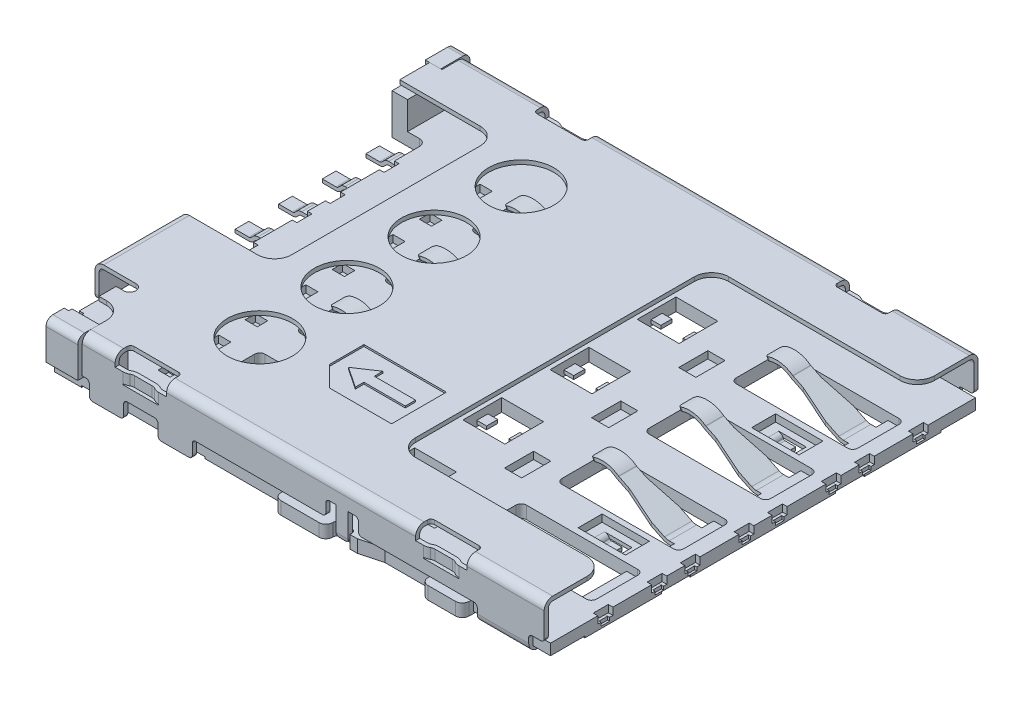
SolidWorks part; units mm, degrees
ref_plane "Front Plane" through (0, 0, 0) normal (0, 0, 1) x (1, 0, 0)
ref_plane "Top Plane" through (0, 0, 0) normal (0, 1, 0) x (1, 0, 0)
ref_plane "Right Plane" through (0, 0, 0) normal (1, 0, 0) x (0, 0, -1)
sketch "Sketch1" plane through (0, 0, 0) normal (0, 1, 0) x (1, 0, 0)
  line L0 (-7.5, 6.21) -> (-7.5, 4.64)
  line L1 (-7.5, 4.64) -> (-7.15, 4.64)
  line L2 (-6.95, 4.44) -> (-6.95, 3.71)
  line L6 (-6.95, 3.27) -> (-6.95, 2.14)
  line L10 (-6.95, 1.7) -> (-6.95, 1.17)
  line L14 (-6.95, 0.73) -> (-6.95, -0.4)
  line L18 (-6.95, -0.84) -> (-6.95, -1.37)
  line L22 (-6.95, -1.81) -> (-6.95, -2.94)
  line L26 (-6.95, -3.38) -> (-6.95, -3.91)
  line L29 (-6.815, -4.35) -> (-6.6639, -4.35) construction
  line L30 (-6.6639, -4.35) -> (-5.3139, -5.7) construction
  line L31 (-5.3139, -5.7) -> (-5.3139, -6.2) construction
  line L32 (-5.3139, -6.2) -> (-0.23, -6.2)
  line L33 (-0.23, -6.2) -> (-0.23, -6.32)
  line L34 (-0.03, -6.52) -> (1.08, -6.52)
  line L35 (1.28, -6.32) -> (1.28, -6.3)
  line L36 (1.38, -6.2) -> (1.73, -6.2)
  line L37 (1.83, -6.3) -> (1.83, -6.37)
  line L38 (1.83, -6.37) -> (2.0456, -6.37)
  line L39 (2.0456, -6.37) -> (2.68, -6.2)
  line L40 (2.68, -6.2) -> (4.06, -6.2)
  line L41 (4.06, -6.2) -> (4.06, -6.32)
  line L42 (4.26, -6.52) -> (5.06, -6.52)
  line L43 (5.26, -6.32) -> (5.26, -6.19)
  line L44 (5.26, -6.19) -> (7.5, -6.19)
  line L45 (7.5, -6.19) -> (7.5, -4.81)
  line L49 (7.5, -4.37) -> (7.5, -3.24)
  line L53 (7.5, -2.8) -> (7.5, -2.27)
  line L57 (7.5, -1.83) -> (7.5, -0.7)
  line L61 (7.5, -0.26) -> (7.5, 0.27)
  line L65 (7.5, 0.71) -> (7.5, 1.84)
  line L69 (7.5, 2.28) -> (7.5, 2.81)
  line L73 (7.5, 3.25) -> (7.5, 4.38)
  line L77 (7.5, 4.82) -> (7.5, 6.2)
  line L78 (7.5, 6.2) -> (5.26, 6.2)
  line L79 (5.26, 6.2) -> (5.26, 6.33)
  line L80 (5.06, 6.53) -> (4.26, 6.53)
  line L81 (4.06, 6.33) -> (4.06, 6.21)
  line L82 (4.06, 6.21) -> (2.68, 6.21)
  line L83 (2.68, 6.21) -> (2.0456, 6.38)
  line L84 (2.0456, 6.38) -> (1.83, 6.38)
  line L85 (1.83, 6.38) -> (1.83, 6.31)
  line L86 (1.73, 6.21) -> (1.38, 6.21)
  line L87 (1.28, 6.31) -> (1.28, 6.33)
  line L88 (1.08, 6.53) -> (-0.03, 6.53)
  line L89 (-0.23, 6.33) -> (-0.23, 6.21)
  line L90 (-0.23, 6.21) -> (-7.5, 6.21)
  line L91 (-7.5, 4.64) -> (-7.5, -6.2) construction
  line L92 (-7.5, -6.2) -> (-6.95, -6.2) construction
  line L93 (7.5, 6.2) -> (-7.5, -6.2) construction
  line L94 (-6.95, 3.71) -> (-6.95, 3.27)
  line L95 (-6.95, 2.14) -> (-6.95, 1.7)
  line L96 (-6.95, 1.17) -> (-6.95, 0.73)
  line L97 (-6.95, -0.4) -> (-6.95, -0.84)
  line L98 (-6.95, -1.37) -> (-6.95, -1.81)
  line L99 (-6.95, -2.94) -> (-6.95, -3.38)
  line L100 (-6.95, -3.91) -> (-6.95, -4.35)
  line L101 (-6.95, -4.35) -> (-6.815, -4.35) construction
  line L102 (7.5, -4.81) -> (7.5, -4.37)
  line L103 (7.5, -3.24) -> (7.5, -2.8)
  line L104 (7.5, -2.27) -> (7.5, -1.83)
  line L105 (7.5, -0.7) -> (7.5, -0.26)
  line L106 (7.5, 0.27) -> (7.5, 0.71)
  line L107 (7.5, 1.84) -> (7.5, 2.28)
  line L108 (7.5, 2.81) -> (7.5, 3.25)
  line L109 (7.5, 4.38) -> (7.5, 4.82)
  line L110 (-6.95, -4.35) -> (-6.95, -6.2)
  line L111 (-6.95, -6.2) -> (-5.3139, -6.2)
  arc A0 (-6.95, 4.44) -> (-7.15, 4.64) centre (-7.15, 4.44) ccw
  arc A1 (-0.23, -6.32) -> (-0.03, -6.52) centre (-0.03, -6.32) ccw
  arc A2 (1.08, -6.52) -> (1.28, -6.32) centre (1.08, -6.32) ccw
  arc A3 (1.38, -6.2) -> (1.28, -6.3) centre (1.38, -6.3) ccw
  arc A4 (1.83, -6.3) -> (1.73, -6.2) centre (1.73, -6.3) ccw
  arc A5 (4.06, -6.32) -> (4.26, -6.52) centre (4.26, -6.32) ccw
  arc A6 (5.06, -6.52) -> (5.26, -6.32) centre (5.06, -6.32) ccw
  arc A7 (5.26, 6.33) -> (5.06, 6.53) centre (5.06, 6.33) ccw
  arc A8 (4.26, 6.53) -> (4.06, 6.33) centre (4.26, 6.33) ccw
  arc A9 (1.73, 6.21) -> (1.83, 6.31) centre (1.73, 6.31) ccw
  arc A10 (1.28, 6.31) -> (1.38, 6.21) centre (1.38, 6.31) ccw
  arc A11 (1.28, 6.33) -> (1.08, 6.53) centre (1.08, 6.33) ccw
  arc A12 (-0.03, 6.53) -> (-0.23, 6.33) centre (-0.03, 6.33) ccw
extrude "Boss-Extrude1" add sketch "Sketch1" along normal blind 0.37
sketch "Sketch2" plane through (-58.2789, 0.37, -33.3165) normal (0, 1, 0) x (1, 0, 0)
  line L0 (60.6874, -30.6765) -> (61.1874, -30.6765)
  line L1 (61.1874, -30.6765) -> (61.1874, -29.8265)
  line L2 (61.1874, -29.8265) -> (60.6874, -29.8265)
  line L3 (60.6874, -29.8265) -> (60.6874, -30.6765)
  line L4 (61.1874, -33.2165) -> (61.1874, -32.3665)
  line L5 (60.6874, -33.2165) -> (61.1874, -33.2165)
  line L6 (60.6874, -32.3665) -> (60.6874, -33.2165)
  line L7 (60.6874, -32.3665) -> (61.1874, -32.3665)
  line L8 (61.1874, -35.7565) -> (61.1874, -34.9065)
  line L9 (61.1874, -34.9065) -> (60.6874, -34.9065)
  line L10 (60.6874, -34.9065) -> (60.6874, -35.7565)
  line L11 (60.6874, -35.7565) -> (61.1874, -35.7565)
  line L12 (60.6874, -38.2965) -> (61.1874, -38.2965)
  line L13 (61.1874, -37.4465) -> (61.1874, -38.2965)
  line L14 (61.1874, -37.4465) -> (60.6874, -37.4465)
  line L15 (60.6874, -37.4465) -> (60.6874, -38.2965)
  line L16 (60.0874, -36.5565) -> (60.0874, -37.6865)
  line L17 (60.0874, -37.6865) -> (58.8674, -37.6865)
  line L18 (58.8674, -36.5565) -> (58.8674, -37.6865)
  line L19 (60.0874, -36.5565) -> (58.8674, -36.5565)
  line L20 (60.0874, -34.0165) -> (60.0874, -35.1465)
  line L21 (60.0874, -35.1465) -> (58.8674, -35.1465)
  line L22 (58.8674, -34.0165) -> (58.8674, -35.1465)
  line L23 (60.0874, -34.0165) -> (58.8674, -34.0165)
  line L24 (60.0874, -31.4765) -> (60.0874, -32.6065)
  line L25 (60.0874, -32.6065) -> (58.8674, -32.6065)
  line L26 (58.8674, -31.4765) -> (58.8674, -32.6065)
  line L27 (60.0874, -31.4765) -> (58.8674, -31.4765)
  line L28 (60.0874, -30.0665) -> (58.8674, -30.0665)
  line L29 (60.0874, -28.9365) -> (60.0874, -30.0665)
  line L30 (60.0874, -28.9365) -> (58.8674, -28.9365)
  line L31 (58.8674, -28.9365) -> (58.8674, -30.0665)
  line L32 (53.5174, -38.029) -> (53.5174, -38.334)
  line L33 (53.1624, -38.334) -> (53.5174, -38.334)
  line L34 (53.1624, -38.029) -> (53.1624, -38.334)
  line L35 (53.1624, -38.029) -> (53.5174, -38.029)
  line L36 (53.1624, -37.294) -> (53.5174, -37.294)
  line L37 (53.5174, -37.294) -> (53.5174, -36.564)
  line L38 (53.1624, -36.564) -> (53.5174, -36.564)
  line L39 (53.1624, -36.564) -> (53.1624, -37.294)
  line L40 (53.5174, -35.794) -> (53.5174, -35.489)
  line L41 (53.1624, -35.794) -> (53.5174, -35.794)
  line L42 (53.1624, -35.489) -> (53.1624, -35.794)
  line L43 (53.1624, -35.489) -> (53.5174, -35.489)
  line L44 (53.5174, -34.754) -> (53.5174, -34.024)
  line L45 (53.1624, -34.754) -> (53.5174, -34.754)
  line L46 (53.1624, -34.024) -> (53.1624, -34.754)
  line L47 (53.5174, -34.024) -> (53.1624, -34.024)
  line L48 (53.1624, -32.949) -> (53.1624, -33.254)
  line L49 (53.1624, -33.254) -> (53.5174, -33.254)
  line L50 (53.5174, -33.254) -> (53.5174, -32.949)
  line L51 (53.1624, -32.949) -> (53.5174, -32.949)
  line L52 (53.1624, -32.214) -> (53.5174, -32.214)
  line L53 (53.5174, -32.214) -> (53.5174, -31.484)
  line L54 (53.1624, -31.484) -> (53.1624, -32.214)
  line L55 (53.1624, -31.484) -> (53.5174, -31.484)
  line L56 (53.1624, -30.714) -> (53.5174, -30.714)
  line L57 (53.5174, -30.714) -> (53.5174, -30.409)
  line L58 (53.5174, -30.409) -> (53.1624, -30.409)
  line L59 (53.1624, -30.409) -> (53.1624, -30.714)
  line L60 (53.1624, -29.674) -> (53.5174, -29.674)
  line L61 (53.5174, -29.674) -> (53.5174, -28.944)
  line L62 (53.5174, -28.944) -> (53.1624, -28.944)
  line L63 (53.1624, -28.944) -> (53.1624, -29.674)
  line L64 (61.7874, -37.7215) -> (61.7874, -36.5215)
  line L65 (65.1874, -37.8715) -> (61.9374, -37.8715)
  line L66 (65.3374, -36.5215) -> (65.3374, -37.7215)
  line L67 (61.9374, -36.3715) -> (65.1874, -36.3715)
  line L68 (65.1874, -35.3315) -> (61.9374, -35.3315)
  line L69 (65.3374, -33.9815) -> (65.3374, -35.1815)
  line L70 (61.9374, -33.8315) -> (65.1874, -33.8315)
  line L71 (61.7874, -35.1815) -> (61.7874, -33.9815)
  line L72 (61.7874, -32.6415) -> (61.7874, -31.4415)
  line L73 (65.1874, -32.7915) -> (61.9374, -32.7915)
  line L74 (65.3374, -31.4415) -> (65.3374, -32.6415)
  line L75 (61.9374, -31.2915) -> (65.1874, -31.2915)
  line L76 (65.1874, -30.2515) -> (61.9374, -30.2515)
  line L77 (65.3374, -28.9015) -> (65.3374, -30.1015)
  line L78 (61.9374, -28.7515) -> (65.1874, -28.7515)
  line L79 (61.7874, -30.1015) -> (61.7874, -28.9015)
  line L80 (54.3174, -31.2915) -> (57.5674, -31.2915)
  line L81 (54.1674, -32.6415) -> (54.1674, -31.4415)
  line L82 (57.5674, -32.7915) -> (54.3174, -32.7915)
  line L83 (54.3174, -33.8315) -> (57.5674, -33.8315)
  line L84 (54.1674, -35.1815) -> (54.1674, -33.9815)
  line L85 (57.5674, -35.3315) -> (54.3174, -35.3315)
  line L86 (54.1674, -37.7215) -> (54.1674, -36.5215)
  line L87 (57.5674, -37.8715) -> (54.3174, -37.8715)
  line L88 (54.3174, -36.3715) -> (57.5674, -36.3715)
  line L89 (57.7174, -36.5215) -> (57.7174, -37.7215)
  line L90 (57.7174, -33.9815) -> (57.7174, -35.1815)
  line L91 (57.7174, -31.4415) -> (57.7174, -32.6415)
  line L92 (57.7174, -28.9015) -> (57.7174, -30.1015)
  line L93 (54.3174, -28.7515) -> (57.5674, -28.7515)
  line L94 (54.1674, -30.1015) -> (54.1674, -28.9015)
  line L95 (57.5674, -30.2515) -> (54.3174, -30.2515)
  line L96 (64.6489, -30.4315) -> (64.6489, -31.1315)
  line L97 (63.2689, -30.4315) -> (64.6489, -30.4315)
  line L98 (63.2689, -31.1315) -> (63.2689, -30.4315)
  line L99 (64.6489, -31.1315) -> (63.2689, -31.1315)
  line L100 (63.2689, -36.1915) -> (64.6489, -36.1915)
  line L101 (64.6489, -35.4915) -> (64.6489, -36.1915)
  line L102 (64.6489, -35.4915) -> (63.2689, -35.4915)
  line L103 (63.2689, -36.1915) -> (63.2689, -35.4915)
  arc A0 (61.7874, -37.7215) -> (61.9374, -37.8715) centre (61.9374, -37.7215) ccw
  arc A1 (65.1874, -37.8715) -> (65.3374, -37.7215) centre (65.1874, -37.7215) ccw
  arc A2 (65.3374, -36.5215) -> (65.1874, -36.3715) centre (65.1874, -36.5215) ccw
  arc A3 (61.9374, -36.3715) -> (61.7874, -36.5215) centre (61.9374, -36.5215) ccw
  arc A4 (61.7874, -35.1815) -> (61.9374, -35.3315) centre (61.9374, -35.1815) ccw
  arc A5 (65.1874, -35.3315) -> (65.3374, -35.1815) centre (65.1874, -35.1815) ccw
  arc A6 (65.3374, -33.9815) -> (65.1874, -33.8315) centre (65.1874, -33.9815) ccw
  arc A7 (61.9374, -33.8315) -> (61.7874, -33.9815) centre (61.9374, -33.9815) ccw
  arc A8 (61.7874, -32.6415) -> (61.9374, -32.7915) centre (61.9374, -32.6415) ccw
  arc A9 (65.1874, -32.7915) -> (65.3374, -32.6415) centre (65.1874, -32.6415) ccw
  arc A10 (65.3374, -31.4415) -> (65.1874, -31.2915) centre (65.1874, -31.4415) ccw
  arc A11 (61.9374, -31.2915) -> (61.7874, -31.4415) centre (61.9374, -31.4415) ccw
  arc A12 (61.7874, -30.1015) -> (61.9374, -30.2515) centre (61.9374, -30.1015) ccw
  arc A13 (65.1874, -30.2515) -> (65.3374, -30.1015) centre (65.1874, -30.1015) ccw
  arc A14 (65.3374, -28.9015) -> (65.1874, -28.7515) centre (65.1874, -28.9015) ccw
  arc A15 (61.9374, -28.7515) -> (61.7874, -28.9015) centre (61.9374, -28.9015) ccw
  arc A16 (54.3174, -31.2915) -> (54.1674, -31.4415) centre (54.3174, -31.4415) ccw
  arc A17 (54.1674, -32.6415) -> (54.3174, -32.7915) centre (54.3174, -32.6415) ccw
  arc A18 (57.7174, -31.4415) -> (57.5674, -31.2915) centre (57.5674, -31.4415) ccw
  arc A19 (57.5674, -32.7915) -> (57.7174, -32.6415) centre (57.5674, -32.6415) ccw
  arc A20 (57.7174, -33.9815) -> (57.5674, -33.8315) centre (57.5674, -33.9815) ccw
  arc A21 (54.3174, -33.8315) -> (54.1674, -33.9815) centre (54.3174, -33.9815) ccw
  arc A22 (54.1674, -35.1815) -> (54.3174, -35.3315) centre (54.3174, -35.1815) ccw
  arc A23 (57.5674, -35.3315) -> (57.7174, -35.1815) centre (57.5674, -35.1815) ccw
  arc A24 (54.3174, -36.3715) -> (54.1674, -36.5215) centre (54.3174, -36.5215) ccw
  arc A25 (54.1674, -37.7215) -> (54.3174, -37.8715) centre (54.3174, -37.7215) ccw
  arc A26 (57.5674, -37.8715) -> (57.7174, -37.7215) centre (57.5674, -37.7215) ccw
  arc A27 (57.7174, -36.5215) -> (57.5674, -36.3715) centre (57.5674, -36.5215) ccw
  arc A28 (57.5674, -30.2515) -> (57.7174, -30.1015) centre (57.5674, -30.1015) ccw
  arc A29 (57.7174, -28.9015) -> (57.5674, -28.7515) centre (57.5674, -28.9015) ccw
  arc A30 (54.3174, -28.7515) -> (54.1674, -28.9015) centre (54.3174, -28.9015) ccw
  arc A31 (54.1674, -30.1015) -> (54.3174, -30.2515) centre (54.3174, -30.1015) ccw
extrude "Cut-Extrude1" cut sketch "Sketch2" against normal through all
sketch "Sketch3" plane through (0, 0.37, 0) normal (0, 1, 0) x (1, 0, 0)
  line L0 (7.5, -4.81) -> (7.365, -4.81)
  line L1 (7.365, -4.37) -> (7.365, -4.81)
  line L2 (7.365, -4.37) -> (7.5, -4.37)
  line L3 (7.5, -3.24) -> (7.365, -3.24)
  line L4 (7.365, -3.24) -> (7.365, -2.8)
  line L5 (7.5, -2.8) -> (7.365, -2.8)
  line L6 (7.5, -2.27) -> (7.365, -2.27)
  line L7 (7.365, -1.83) -> (7.365, -2.27)
  line L8 (7.5, -1.83) -> (7.365, -1.83)
  line L9 (7.5, -0.7) -> (7.365, -0.7)
  line L10 (7.365, -0.7) -> (7.365, -0.26)
  line L11 (7.365, -0.26) -> (7.5, -0.26)
  line L12 (7.365, 0.27) -> (7.5, 0.27)
  line L13 (7.365, 0.71) -> (7.365, 0.27)
  line L14 (7.365, 0.71) -> (7.5, 0.71)
  line L15 (7.5, 1.84) -> (7.365, 1.84)
  line L16 (7.365, 1.84) -> (7.365, 2.28)
  line L17 (7.5, 2.28) -> (7.365, 2.28)
  line L18 (7.5, 2.81) -> (7.365, 2.81)
  line L19 (7.365, 3.25) -> (7.365, 2.81)
  line L20 (7.365, 3.25) -> (7.5, 3.25)
  line L21 (7.365, 4.38) -> (7.5, 4.38)
  line L22 (7.365, 4.38) -> (7.365, 4.82)
  line L23 (7.5, 4.82) -> (7.365, 4.82)
  line L24 (-6.95, -5.92) -> (-6.815, -5.92)
  line L25 (-6.815, -5.92) -> (-6.815, -5.48)
  line L27 (-6.95, -5.48) -> (-6.815, -5.48)
  line L28 (-6.95, -4.35) -> (-6.815, -4.35)
  line L29 (-6.815, -4.35) -> (-6.815, -3.91)
  line L30 (-6.95, -3.91) -> (-6.815, -3.91)
  line L31 (-6.815, -3.38) -> (-6.95, -3.38)
  line L32 (-6.815, -2.94) -> (-6.815, -3.38)
  line L33 (-6.815, -2.94) -> (-6.95, -2.94)
  line L34 (-6.815, -1.81) -> (-6.95, -1.81)
  line L35 (-6.815, -1.81) -> (-6.815, -1.37)
  line L36 (-6.815, -1.37) -> (-6.95, -1.37)
  line L37 (-6.815, -0.84) -> (-6.95, -0.84)
  line L38 (-6.815, -0.4) -> (-6.815, -0.84)
  line L39 (-6.815, -0.4) -> (-6.95, -0.4)
  line L40 (-6.815, 0.73) -> (-6.95, 0.73)
  line L41 (-6.815, 0.73) -> (-6.815, 1.17)
  line L42 (-6.95, 1.17) -> (-6.815, 1.17)
  line L43 (-6.815, 1.7) -> (-6.95, 1.7)
  line L44 (-6.815, 2.14) -> (-6.815, 1.7)
  line L45 (-6.95, 2.14) -> (-6.815, 2.14)
  line L46 (-6.95, 3.27) -> (-6.815, 3.27)
  line L47 (-6.815, 3.27) -> (-6.815, 3.71)
  line L48 (-6.815, 3.71) -> (-6.95, 3.71)
  line L49 (-6.95, -4.35) -> (-6.95, -3.91)
  line L50 (-6.95, -3.38) -> (-6.95, -2.94)
  line L51 (-6.95, -1.81) -> (-6.95, -1.37)
  line L52 (-6.95, -0.84) -> (-6.95, -0.4)
  line L53 (-6.95, 0.73) -> (-6.95, 1.17)
  line L54 (-6.95, 1.7) -> (-6.95, 2.14)
  line L55 (-6.95, 3.27) -> (-6.95, 3.71)
  line L56 (7.5, 4.38) -> (7.5, 4.82)
  line L57 (7.5, 2.81) -> (7.5, 3.25)
  line L58 (7.5, 1.84) -> (7.5, 2.28)
  line L59 (7.5, 0.27) -> (7.5, 0.71)
  line L60 (7.5, -0.7) -> (7.5, -0.26)
  line L61 (7.5, -2.27) -> (7.5, -1.83)
  line L62 (7.5, -3.24) -> (7.5, -2.8)
  line L63 (7.5, -4.81) -> (7.5, -4.37)
  line L64 (-6.95, -5.92) -> (-6.95, -5.48)
extrude "Cut-Extrude2" cut sketch "Sketch3" against normal blind 0.21
sketch "Sketch4" plane through (0, 0.16, 0) normal (0, 1, 0) x (1, 0, 0)
  line L0 (7.5, -4.465) -> (7.365, -4.465)
  line L1 (7.365, -4.715) -> (7.5, -4.715)
  line L2 (7.5, -2.895) -> (7.365, -2.895)
  line L3 (7.365, -3.145) -> (7.5, -3.145)
  line L4 (7.5, -1.925) -> (7.365, -1.925)
  line L5 (7.365, -2.175) -> (7.5, -2.175)
  line L6 (7.5, -0.355) -> (7.365, -0.355)
  line L7 (7.365, -0.605) -> (7.5, -0.605)
  line L8 (7.5, 0.615) -> (7.365, 0.615)
  line L9 (7.365, 0.365) -> (7.5, 0.365)
  line L10 (7.5, 2.185) -> (7.365, 2.185)
  line L11 (7.365, 1.935) -> (7.5, 1.935)
  line L12 (7.5, 3.155) -> (7.365, 3.155)
  line L13 (7.365, 2.905) -> (7.5, 2.905)
  line L14 (7.5, 4.725) -> (7.365, 4.725)
  line L15 (7.365, 4.475) -> (7.5, 4.475)
  line L16 (-6.95, -5.575) -> (-6.815, -5.575)
  line L17 (-6.95, -5.825) -> (-6.815, -5.825)
  line L18 (-6.95, -4.255) -> (-6.815, -4.255)
  line L19 (-6.815, -4.005) -> (-6.95, -4.005)
  line L20 (-6.95, -3.285) -> (-6.815, -3.285)
  line L21 (-6.815, -3.035) -> (-6.95, -3.035)
  line L22 (-6.95, -1.715) -> (-6.815, -1.715)
  line L23 (-6.815, -1.465) -> (-6.95, -1.465)
  line L24 (-6.95, -0.745) -> (-6.815, -0.745)
  line L25 (-6.815, -0.495) -> (-6.95, -0.495)
  line L26 (-6.95, 0.825) -> (-6.815, 0.825)
  line L27 (-6.815, 1.075) -> (-6.95, 1.075)
  line L28 (-6.95, 1.795) -> (-6.815, 1.795)
  line L29 (-6.815, 2.045) -> (-6.95, 2.045)
  line L30 (-6.95, 3.365) -> (-6.815, 3.365)
  line L31 (-6.815, 3.615) -> (-6.95, 3.615)
  line L32 (-6.95, 3.615) -> (-6.95, 3.365)
  line L33 (-6.95, 2.045) -> (-6.95, 1.795)
  line L34 (-6.95, 1.075) -> (-6.95, 0.825)
  line L35 (-6.95, -0.495) -> (-6.95, -0.745)
  line L36 (-6.95, -1.465) -> (-6.95, -1.715)
  line L37 (-6.95, -3.035) -> (-6.95, -3.285)
  line L38 (-6.95, -4.005) -> (-6.95, -4.255)
  line L39 (7.5, 4.725) -> (7.5, 4.475)
  line L40 (7.5, 3.155) -> (7.5, 2.905)
  line L41 (7.5, 2.185) -> (7.5, 1.935)
  line L42 (7.5, 0.615) -> (7.5, 0.365)
  line L43 (7.5, -0.355) -> (7.5, -0.605)
  line L44 (7.5, -1.925) -> (7.5, -2.175)
  line L45 (7.5, -2.895) -> (7.5, -3.145)
  line L46 (7.5, -4.465) -> (7.5, -4.715)
  line L47 (-6.815, 3.615) -> (-6.815, 3.365)
  line L48 (-6.815, 2.045) -> (-6.815, 1.795)
  line L50 (-6.815, 1.075) -> (-6.815, 0.825)
  line L52 (-6.815, -0.745) -> (-6.815, -0.495)
  line L54 (-6.815, -1.715) -> (-6.815, -1.465)
  line L56 (-6.815, -3.285) -> (-6.815, -3.035)
  line L59 (-6.815, -4.005) -> (-6.815, -4.255)
  line L61 (7.365, 4.725) -> (7.365, 4.475)
  line L62 (7.365, 3.155) -> (7.365, 2.905)
  line L64 (7.365, 2.185) -> (7.365, 1.935)
  line L65 (7.365, 0.615) -> (7.365, 0.365)
  line L67 (7.365, -0.605) -> (7.365, -0.355)
  line L69 (7.365, -1.925) -> (7.365, -2.175)
  line L72 (7.365, -2.895) -> (7.365, -3.145)
  line L74 (7.365, -4.465) -> (7.365, -4.715)
  line L76 (-6.815, -5.575) -> (-6.815, -5.825)
  line L78 (-6.95, -5.825) -> (-6.95, -5.575)
extrude "Cut-Extrude3" cut sketch "Sketch4" against normal blind 0.1
sketch "Sketch5" plane through (0, 0.06, 0) normal (0, 1, 0) x (1, 0, 0)
  line L0 (-6.65, 3.615) -> (-6.89, 3.615)
  line L1 (-6.89, 3.615) -> (-6.89, 3.365)
  line L2 (-6.89, 3.365) -> (-6.8, 3.365)
  line L3 (-6.8, 3.365) -> (-6.8, 2.045)
  line L4 (-6.8, 2.045) -> (-6.89, 2.045)
  line L5 (-6.89, 2.045) -> (-6.89, 1.795)
  line L6 (-6.89, 1.795) -> (-6.8, 1.795)
  line L7 (-6.8, 1.795) -> (-6.8, 1.075)
  line L8 (-6.8, 1.075) -> (-6.89, 1.075)
  line L9 (-6.89, 1.075) -> (-6.89, 0.825)
  line L10 (-6.89, 0.825) -> (-6.8, 0.825)
  line L11 (-6.8, 0.825) -> (-6.8, -0.495)
  line L12 (-6.8, -0.495) -> (-6.89, -0.495)
  line L13 (-6.89, -0.495) -> (-6.89, -0.745)
  line L14 (-6.89, -0.745) -> (-6.8, -0.745)
  line L15 (-6.8, -0.745) -> (-6.8, -1.465)
  line L16 (-6.8, -1.465) -> (-6.89, -1.465)
  line L17 (-6.89, -1.465) -> (-6.89, -1.715)
  line L18 (-6.89, -1.715) -> (-6.8, -1.715)
  line L19 (-6.8, -1.715) -> (-6.8, -3.035)
  line L20 (-6.8, -3.035) -> (-6.89, -3.035)
  line L21 (-6.89, -3.035) -> (-6.89, -3.285)
  line L22 (-6.89, -3.285) -> (-6.8, -3.285)
  line L23 (-6.8, -3.285) -> (-6.8, -4.005)
  line L24 (-6.8, -4.005) -> (-6.89, -4.005)
  line L25 (-6.89, -4.005) -> (-6.89, -4.255)
  line L26 (-6.89, -4.255) -> (-6.8, -4.255)
  line L27 (-6.8, -4.255) -> (-6.8, -5.575)
  line L28 (-6.8, -5.575) -> (-6.89, -5.575)
  line L29 (-6.89, -5.575) -> (-6.89, -5.825)
  line L30 (-6.89, -5.825) -> (-6.65, -5.825)
  line L31 (-6.65, -5.825) -> (-6.65, 3.615)
  line L32 (7.2, -4.715) -> (7.44, -4.715)
  line L33 (7.44, -4.715) -> (7.44, -4.465)
  line L34 (7.44, -4.465) -> (7.35, -4.465)
  line L35 (7.35, -4.465) -> (7.35, -3.145)
  line L36 (7.35, -3.145) -> (7.44, -3.145)
  line L37 (7.44, -3.145) -> (7.44, -2.895)
  line L38 (7.44, -2.895) -> (7.35, -2.895)
  line L39 (7.35, -2.895) -> (7.35, -2.175)
  line L40 (7.35, -2.175) -> (7.44, -2.175)
  line L41 (7.44, -2.175) -> (7.44, -1.925)
  line L42 (7.44, -1.925) -> (7.35, -1.925)
  line L43 (7.35, -1.925) -> (7.35, -0.605)
  line L44 (7.35, -0.605) -> (7.44, -0.605)
  line L45 (7.44, -0.605) -> (7.44, -0.355)
  line L46 (7.44, -0.355) -> (7.35, -0.355)
  line L47 (7.35, -0.355) -> (7.35, 0.365)
  line L48 (7.35, 0.365) -> (7.44, 0.365)
  line L49 (7.44, 0.365) -> (7.44, 0.615)
  line L50 (7.44, 0.615) -> (7.35, 0.615)
  line L51 (7.35, 0.615) -> (7.35, 1.935)
  line L52 (7.35, 1.935) -> (7.44, 1.935)
  line L53 (7.44, 1.935) -> (7.44, 2.185)
  line L54 (7.44, 2.185) -> (7.35, 2.185)
  line L55 (7.35, 2.185) -> (7.35, 2.905)
  line L56 (7.35, 2.905) -> (7.44, 2.905)
  line L57 (7.44, 2.905) -> (7.44, 3.155)
  line L58 (7.44, 3.155) -> (7.35, 3.155)
  line L59 (7.35, 3.155) -> (7.35, 4.475)
  line L60 (7.35, 4.475) -> (7.44, 4.475)
  line L61 (7.44, 4.475) -> (7.44, 4.725)
  line L62 (7.44, 4.725) -> (7.2, 4.725)
  line L63 (7.2, 4.725) -> (7.2, -4.715)
  line L64 (6.5855, 4.215) -> (6.4355, 4.215)
  line L65 (6.4355, 4.215) -> (6.4355, 3.415)
  line L66 (6.4355, 3.415) -> (6.5855, 3.415)
  line L67 (6.5855, 3.415) -> (6.5855, 1.675)
  line L68 (6.5855, 1.675) -> (6.4355, 1.675)
  line L69 (6.4355, 1.675) -> (6.4355, 0.875)
  line L70 (6.4355, 0.875) -> (6.5855, 0.875)
  line L71 (6.5855, 0.875) -> (6.5855, -0.865)
  line L72 (6.5855, -0.865) -> (6.4355, -0.865)
  line L73 (6.4355, -0.865) -> (6.4355, -1.665)
  line L74 (6.4355, -1.665) -> (6.5855, -1.665)
  line L75 (6.5855, -1.665) -> (6.5855, -4.555)
  line L76 (6.5855, -4.555) -> (7.0585, -4.555)
  line L77 (7.0585, -4.555) -> (7.0585, 4.565)
  line L78 (7.0585, 4.565) -> (6.5855, 4.565)
  line L79 (6.5855, 4.565) -> (6.5855, 4.215)
  line L80 (-1.0345, 4.215) -> (-1.1845, 4.215)
  line L81 (-1.1845, 4.215) -> (-1.1845, 3.415)
  line L82 (-1.1845, 3.415) -> (-1.0345, 3.415)
  line L83 (-1.0345, 3.415) -> (-1.0345, 1.675)
  line L84 (-1.0345, 1.675) -> (-1.1845, 1.675)
  line L85 (-1.1845, 1.675) -> (-1.1845, 0.875)
  line L86 (-1.1845, 0.875) -> (-1.0345, 0.875)
  line L87 (-1.0345, 0.875) -> (-1.0345, -0.865)
  line L88 (-1.0345, -0.865) -> (-1.1845, -0.865)
  line L89 (-1.1845, -0.865) -> (-1.1845, -1.665)
  line L90 (-1.1845, -1.665) -> (-1.0345, -1.665)
  line L91 (-1.0345, -1.665) -> (-1.0345, -4.555)
  line L92 (-1.0345, -4.555) -> (-0.5615, -4.555)
  line L93 (-0.5615, -4.555) -> (-0.5615, 4.565)
  line L94 (-0.5615, 4.565) -> (-1.0345, 4.565)
  line L95 (-1.0345, 4.565) -> (-1.0345, 4.215)
  line L96 (2.4085, -4.13) -> (2.4085, -4.98)
  line L97 (2.4085, -4.98) -> (2.9085, -4.98)
  line L98 (2.9085, -4.98) -> (2.9085, -4.13)
  line L99 (2.9085, -4.13) -> (2.4085, -4.13)
  line L100 (2.4085, -1.59) -> (2.4085, -2.44)
  line L101 (2.4085, -2.44) -> (2.9085, -2.44)
  line L102 (2.9085, -2.44) -> (2.9085, -1.59)
  line L103 (2.9085, -1.59) -> (2.4085, -1.59)
  line L104 (1.5235, -3.6425) -> (1.5235, -3.9675)
  line L105 (1.5235, -3.9675) -> (1.8085, -3.9675)
  line L106 (1.8085, -3.9675) -> (1.8085, -3.6425)
  line L107 (1.8085, -3.6425) -> (1.5235, -3.6425)
  line L108 (0.5885, -3.6425) -> (0.5885, -3.9675)
  line L109 (0.5885, -3.9675) -> (0.8735, -3.9675)
  line L110 (0.8735, -3.9675) -> (0.8735, -3.6425)
  line L111 (0.8735, -3.6425) -> (0.5885, -3.6425)
  line L112 (0.5885, -1.1025) -> (0.5885, -1.4275)
  line L113 (0.5885, -1.4275) -> (0.8735, -1.4275)
  line L114 (0.8735, -1.4275) -> (0.8735, -1.1025)
  line L115 (0.8735, -1.1025) -> (0.5885, -1.1025)
  line L116 (1.5235, -1.1025) -> (1.5235, -1.4275)
  line L117 (1.5235, -1.4275) -> (1.8085, -1.4275)
  line L118 (1.8085, -1.4275) -> (1.8085, -1.1025)
  line L119 (1.8085, -1.1025) -> (1.5235, -1.1025)
  line L120 (2.4085, 0.95) -> (2.4085, 0.1)
  line L121 (2.4085, 0.1) -> (2.9085, 0.1)
  line L122 (2.9085, 0.1) -> (2.9085, 0.95)
  line L123 (2.9085, 0.95) -> (2.4085, 0.95)
  line L124 (0.5885, 1.4375) -> (0.5885, 1.1125)
  line L125 (0.5885, 1.1125) -> (0.8735, 1.1125)
  line L126 (0.8735, 1.1125) -> (0.8735, 1.4375)
  line L127 (0.8735, 1.4375) -> (0.5885, 1.4375)
  line L128 (1.5235, 1.4375) -> (1.5235, 1.1125)
  line L129 (1.5235, 1.1125) -> (1.8085, 1.1125)
  line L130 (1.8085, 1.1125) -> (1.8085, 1.4375)
  line L131 (1.8085, 1.4375) -> (1.5235, 1.4375)
  line L132 (2.4085, 3.49) -> (2.4085, 2.64)
  line L133 (2.4085, 2.64) -> (2.9085, 2.64)
  line L134 (2.9085, 2.64) -> (2.9085, 3.49)
  line L135 (2.9085, 3.49) -> (2.4085, 3.49)
  line L136 (1.5235, 3.9775) -> (1.5235, 3.6525)
  line L137 (1.5235, 3.6525) -> (1.8085, 3.6525)
  line L138 (1.8085, 3.6525) -> (1.8085, 3.9775)
  line L139 (1.8085, 3.9775) -> (1.5235, 3.9775)
  line L140 (0.5885, 3.9775) -> (0.5885, 3.6525)
  line L141 (0.5885, 3.6525) -> (0.8735, 3.6525)
  line L142 (0.8735, 3.6525) -> (0.8735, 3.9775)
  line L143 (0.8735, 3.9775) -> (0.5885, 3.9775)
  line L144 (-5.1165, 4.3725) -> (-5.1165, 3.6425)
  line L145 (-5.1165, 3.6425) -> (-4.7615, 3.6425)
  line L146 (-4.7615, 3.6425) -> (-4.7615, 4.3725)
  line L147 (-4.7615, 4.3725) -> (-5.1165, 4.3725)
  line L148 (-5.1165, 2.9075) -> (-5.1165, 2.6025)
  line L149 (-5.1165, 2.6025) -> (-4.7615, 2.6025)
  line L150 (-4.7615, 2.6025) -> (-4.7615, 2.9075)
  line L151 (-4.7615, 2.9075) -> (-5.1165, 2.9075)
  line L152 (-5.1165, 1.8325) -> (-5.1165, 1.1025)
  line L153 (-5.1165, 1.1025) -> (-4.7615, 1.1025)
  line L154 (-4.7615, 1.1025) -> (-4.7615, 1.8325)
  line L155 (-4.7615, 1.8325) -> (-5.1165, 1.8325)
  line L156 (-5.1165, 0.3675) -> (-5.1165, 0.0625)
  line L157 (-5.1165, 0.0625) -> (-4.7615, 0.0625)
  line L158 (-4.7615, 0.0625) -> (-4.7615, 0.3675)
  line L159 (-4.7615, 0.3675) -> (-5.1165, 0.3675)
  line L160 (-5.1165, -4.7125) -> (-5.1165, -5.0175)
  line L161 (-5.1165, -5.0175) -> (-4.7615, -5.0175)
  line L162 (-4.7615, -5.0175) -> (-4.7615, -4.7125)
  line L163 (-4.7615, -4.7125) -> (-5.1165, -4.7125)
  line L164 (-5.1165, -3.2475) -> (-5.1165, -3.9775)
  line L165 (-5.1165, -3.9775) -> (-4.7615, -3.9775)
  line L166 (-4.7615, -3.9775) -> (-4.7615, -3.2475)
  line L167 (-4.7615, -3.2475) -> (-5.1165, -3.2475)
  line L168 (-5.1165, -2.1725) -> (-5.1165, -2.4775)
  line L169 (-5.1165, -2.4775) -> (-4.7615, -2.4775)
  line L170 (-4.7615, -2.4775) -> (-4.7615, -2.1725)
  line L171 (-4.7615, -2.1725) -> (-5.1165, -2.1725)
  line L172 (-5.1165, -0.7075) -> (-5.1165, -1.4375)
  line L173 (-5.1165, -1.4375) -> (-4.7615, -1.4375)
  line L174 (-4.7615, -1.4375) -> (-4.7615, -0.7075)
  line L175 (-4.7615, -0.7075) -> (-5.1165, -0.7075)
  line L176 (-6.95, -2.125) -> (-7.2357, -2.125)
  line L177 (-7.2357, -2.125) -> (-7.2357, -2.525)
  line L178 (-7.2357, -2.525) -> (-6.95, -2.525)
  line L179 (-6.95, -2.525) -> (-6.95, -2.125)
  line L180 (-6.95, -0.855) -> (-7.2357, -0.855)
  line L181 (-7.2357, -0.855) -> (-7.2357, -1.255)
  line L182 (-7.2357, -1.255) -> (-6.95, -1.255)
  line L183 (-6.95, -1.255) -> (-6.95, -0.855)
  line L184 (-6.95, 0.415) -> (-7.2357, 0.415)
  line L185 (-7.2357, 0.415) -> (-7.2357, 0.015)
  line L186 (-7.2357, 0.015) -> (-6.95, 0.015)
  line L187 (-6.95, 0.015) -> (-6.95, 0.415)
  line L188 (-6.95, 1.685) -> (-7.2357, 1.685)
  line L189 (-7.2357, 1.685) -> (-7.2357, 1.285)
  line L190 (-7.2357, 1.285) -> (-6.95, 1.285)
  line L191 (-6.95, 1.285) -> (-6.95, 1.685)
  line L192 (-6.95, 2.955) -> (-7.2357, 2.955)
  line L193 (-7.2357, 2.955) -> (-7.2357, 2.555)
  line L194 (-7.2357, 2.555) -> (-6.95, 2.555)
  line L195 (-6.95, 2.555) -> (-6.95, 2.955)
  line L196 (-6.95, 4.225) -> (-7.2357, 4.225)
  line L197 (-7.2357, 4.225) -> (-7.2357, 3.825)
  line L198 (-7.2357, 3.825) -> (-6.95, 3.825)
  line L199 (-6.95, 3.825) -> (-6.95, 4.225)
  line L200 (5.265, -2.69) -> (6.065, -2.69)
  line L202 (6.37, -2.175) -> (4.99, -2.175)
  line L203 (4.99, -2.175) -> (4.99, -2.875)
  line L204 (4.99, -2.875) -> (6.37, -2.875)
  line L205 (6.37, -2.875) -> (6.37, -2.175)
  line L209 (6.065, -2.69) -> (6.065, -2.38)
  line L210 (4.99, 2.885) -> (4.99, 2.185)
  line L211 (4.99, 2.185) -> (6.37, 2.185)
  line L212 (6.37, 2.185) -> (6.37, 2.885)
  line L213 (6.37, 2.885) -> (4.99, 2.885)
  line L214 (6.065, -2.38) -> (5.265, -2.38)
  line L215 (6.065, 2.7) -> (5.265, 2.7)
  line L216 (5.265, 2.39) -> (6.065, 2.39)
  line L217 (6.065, 2.39) -> (6.065, 2.7)
  line L218 (5.265, 2.7) -> (5.265, 2.39)
  line L219 (5.265, -2.38) -> (5.265, -2.69)
  line L220 (7.44, 4.725) -> (7.5, 6.2) construction
  point P14 (7.5, 6.2)
extrude "Boss-Extrude2" add sketch "Sketch5" along normal blind 0.1 separate body
sketch "Sketch8" plane through (0, 0, 2.525) normal (0, 0, 1) x (1, 0, 0)
  line L0 (-7.2357, 0.16) -> (-7.2357, 0.06)
  line L1 (-7.3772, 0.1014) -> (-7.4293, 0.0493)
  line L2 (-7.5, 0.02) -> (-7.9, 0.02)
  line L3 (-7.9, 0.02) -> (-7.9, -0.08)
  line L4 (-7.9, -0.08) -> (-7.5, -0.08)
  line L5 (-7.3586, -0.0214) -> (-7.3064, 0.0307)
  arc A0 (-7.2357, 0.16) -> (-7.3772, 0.1014) centre (-7.2357, -0.04) ccw
  arc A1 (-7.5, 0.02) -> (-7.4293, 0.0493) centre (-7.5, 0.12) ccw
  arc A2 (-7.5, -0.08) -> (-7.3586, -0.0214) centre (-7.5, 0.12) ccw
  arc A3 (-7.2357, 0.06) -> (-7.3064, 0.0307) centre (-7.2357, -0.04) ccw
  point P14 (-7.2357, 0.06)
extrude "Boss-Extrude3" add sketch "Sketch8" against normal blind 0.4
pattern_linear "LPattern1" count 6 spacing 1.27 along (0, 0, -1) of "Boss-Extrude3"
sketch "Sketch9" plane through (0, 0, 1.665) normal (0, 0, 1) x (1, 0, 0)
  line L0 (-3.6126, 0.995) -> (-3.5703, 0.9044)
  line L1 (-2.8355, 0.8191) -> (-2.546, 0.6779)
  line L2 (-2.546, 0.7891) -> (-2.7916, 0.909)
  line L3 (-2.546, 0.6779) -> (-2.4418, 0.6271)
  line L4 (-2.4418, 0.7383) -> (-2.546, 0.7891)
  line L5 (-2.4418, 0.6271) -> (-1.6995, 0.265)
  line L6 (-1.6995, 0.3763) -> (-2.4418, 0.7383)
  line L7 (-1.3204, 0.1914) -> (-1.6995, 0.3763)
  line L8 (-1.6995, 0.265) -> (-1.3642, 0.1015)
  line L9 (-1.1845, 0.06) -> (-1.1845, 0.16)
  line L10 (4.0074, 0.995) -> (4.0497, 0.9044)
  line L11 (4.7845, 0.8191) -> (5.074, 0.6779)
  line L12 (5.074, 0.7891) -> (4.8284, 0.909)
  line L13 (5.074, 0.6779) -> (5.1782, 0.6271)
  line L14 (5.1782, 0.7383) -> (5.074, 0.7891)
  line L15 (5.1782, 0.6271) -> (5.9205, 0.265)
  line L16 (5.9205, 0.3763) -> (5.1782, 0.7383)
  line L17 (6.2996, 0.1914) -> (5.9205, 0.3763)
  line L18 (5.9205, 0.265) -> (6.2558, 0.1015)
  line L19 (6.4355, 0.06) -> (6.4355, 0.16)
  arc A0 (-3.4767, 0.9402) -> (-3.5703, 0.9044) centre (-3.2745, 0.27) ccw
  arc A1 (-3.5193, 1.0316) -> (-3.6126, 0.995) centre (-3.2745, 0.27) ccw
  arc A2 (-2.7994, 0.9137) -> (-3.5193, 1.0316) centre (-3.2745, 0.27) ccw
  arc A3 (-2.8588, 0.8332) -> (-3.4767, 0.9402) centre (-3.2745, 0.27) ccw
  arc A4 (-2.8588, 0.8332) -> (-2.8355, 0.8191) centre (-2.7697, 0.9539) ccw
  arc A5 (-2.7994, 0.9137) -> (-2.7916, 0.909) centre (-2.7697, 0.9539) ccw
  arc A6 (-1.3642, 0.1015) -> (-1.1845, 0.06) centre (-1.1845, 0.47) ccw
  arc A7 (-1.3204, 0.1914) -> (-1.1845, 0.16) centre (-1.1845, 0.47) ccw
  arc A8 (4.1433, 0.9402) -> (4.0497, 0.9044) centre (4.3455, 0.27) ccw
  arc A9 (4.1007, 1.0316) -> (4.0074, 0.995) centre (4.3455, 0.27) ccw
  arc A10 (4.8206, 0.9137) -> (4.1007, 1.0316) centre (4.3455, 0.27) ccw
  arc A11 (4.7612, 0.8332) -> (4.1433, 0.9402) centre (4.3455, 0.27) ccw
  arc A12 (4.7612, 0.8332) -> (4.7845, 0.8191) centre (4.8503, 0.9539) ccw
  arc A13 (4.8206, 0.9137) -> (4.8284, 0.909) centre (4.8503, 0.9539) ccw
  arc A14 (6.2558, 0.1015) -> (6.4355, 0.06) centre (6.4355, 0.47) ccw
  arc A15 (6.2996, 0.1914) -> (6.4355, 0.16) centre (6.4355, 0.47) ccw
  point P52 (-1.1845, 0.06)
extrude "Boss-Extrude4" add sketch "Sketch9" against normal blind 0.8
pattern_linear "LPattern2" count 3 spacing 2.54 along (0, 0, -1) of "Boss-Extrude4"
sketch "Sketch10" plane through (0, 0.16, 0) normal (0, 1, 0) x (1, 0, 0)
  line L0 (5.9205, 4.215) -> (5.1265, 4.075)
  line L1 (5.1265, 3.555) -> (5.9205, 3.415)
  line L2 (4.0074, 3.555) -> (5.1265, 3.555)
  line L3 (5.1265, 4.075) -> (4.0074, 4.075)
  line L4 (4.0074, 4.075) -> (4.0074, 3.555)
  line L5 (-3.6126, 4.075) -> (-3.6126, 3.555)
  line L6 (-2.4935, 4.075) -> (-3.6126, 4.075)
  line L7 (-3.6126, 3.555) -> (-2.4935, 3.555)
  line L8 (-2.4935, 3.555) -> (-1.6995, 3.415)
  line L9 (-1.6995, 4.215) -> (-2.4935, 4.075)
  line L10 (-1.6995, 4.215) -> (-3.7661, 4.215)
  line L11 (-3.7661, 4.215) -> (-3.7661, 3.415)
  line L12 (-3.7661, 3.415) -> (-1.6995, 3.415)
  line L13 (5.9205, 3.415) -> (3.8146, 3.415)
  line L14 (3.8146, 3.415) -> (3.8146, 4.215)
  line L15 (3.8146, 4.215) -> (5.9205, 4.215)
  line L16 (5.9205, 1.675) -> (5.1265, 1.535)
  line L17 (5.1265, 1.015) -> (5.9205, 0.875)
  line L18 (4.0074, 1.015) -> (5.1265, 1.015)
  line L19 (5.1265, 1.535) -> (4.0074, 1.535)
  line L20 (4.0074, 1.535) -> (4.0074, 1.015)
  line L21 (-3.6126, 1.535) -> (-3.6126, 1.015)
  line L22 (-2.4935, 1.535) -> (-3.6126, 1.535)
  line L23 (-3.6126, 1.015) -> (-2.4935, 1.015)
  line L24 (-2.4935, 1.015) -> (-1.6995, 0.875)
  line L25 (-1.6995, 1.675) -> (-2.4935, 1.535)
  line L26 (-1.6995, 1.675) -> (-3.7661, 1.675)
  line L27 (-3.7661, 1.675) -> (-3.7661, 0.875)
  line L28 (-3.7661, 0.875) -> (-1.6995, 0.875)
  line L29 (5.9205, 0.875) -> (3.8146, 0.875)
  line L30 (3.8146, 0.875) -> (3.8146, 1.675)
  line L31 (3.8146, 1.675) -> (5.9205, 1.675)
  line L32 (5.9205, -0.865) -> (5.1265, -1.005)
  line L33 (5.1265, -1.525) -> (5.9205, -1.665)
  line L34 (4.0074, -1.525) -> (5.1265, -1.525)
  line L35 (5.1265, -1.005) -> (4.0074, -1.005)
  line L36 (4.0074, -1.005) -> (4.0074, -1.525)
  line L37 (-3.6126, -1.005) -> (-3.6126, -1.525)
  line L38 (-2.4935, -1.005) -> (-3.6126, -1.005)
  line L39 (-3.6126, -1.525) -> (-2.4935, -1.525)
  line L40 (-2.4935, -1.525) -> (-1.6995, -1.665)
  line L41 (-1.6995, -0.865) -> (-2.4935, -1.005)
  line L42 (-1.6995, -0.865) -> (-3.7661, -0.865)
  line L43 (-3.7661, -0.865) -> (-3.7661, -1.665)
  line L44 (-3.7661, -1.665) -> (-1.6995, -1.665)
  line L45 (5.9205, -1.665) -> (3.8146, -1.665)
  line L46 (3.8146, -1.665) -> (3.8146, -0.865)
  line L47 (3.8146, -0.865) -> (5.9205, -0.865)
  dimension "D1" = 3
extrude "Cut-Extrude4" cut sketch "Sketch10" against normal through all both and the other way through all
fillet "Fillet1" radius 0.1 6 edges at (-3.5915, 0.9497, -4.075) (-3.5915, 0.9497, -3.555) (-3.5915, 0.9497, -1.535) (-3.5915, 0.9497, -1.015) (-3.5915, 0.9497, 1.005) (-3.5915, 0.9497, 1.525)
fillet "Fillet2" radius 0.1 6 edges at (4.0285, 0.9497, -4.075) (4.0285, 0.9497, -3.555) (4.0285, 0.9497, -1.535) (4.0285, 0.9497, -1.015) (4.0285, 0.9497, 1.005) (4.0285, 0.9497, 1.525)
ref_plane "Plane1" through (0, 0, -2.545) normal (0, 0, 1) x (1, 0, 0)
sketch "Sketch11" plane through (0, 0, -2.545) normal (0, 0, 1) x (1, 0, 0)
  line L1 (5.46, -0.08) -> (5.77, -0.08)
  line L2 (5.77, -0.08) -> (5.77, 0.02)
  line L3 (5.77, 0.02) -> (5.46, 0.02)
  line L8 (5.265, 0.06) -> (5.265, 0.16)
  arc A0 (5.3151, 0.024) -> (5.265, 0.06) centre (5.265, 0.0071) ccw
  arc A1 (5.3151, 0.024) -> (5.46, -0.08) centre (5.46, 0.0729) ccw
  arc A2 (5.4099, 0.056) -> (5.46, 0.02) centre (5.46, 0.0729) ccw
  arc A3 (5.4099, 0.056) -> (5.265, 0.16) centre (5.265, 0.0071) ccw
extrude "Boss-Extrude5" add sketch "Sketch11" along normal mid plane 0.29
pattern_linear "LPattern3" count 2 spacing 5.06 along (0, 0, 1) of "Boss-Extrude5"
sketch "Sketch15" plane through (0, 0, 0) normal (0, 1, 0) x (1, 0, 0)
  line L2 (-6.95, -6.2) -> (-5.3139, -6.2)
  line L3 (-5.3139, -6.2) -> (-5.3139, -5.7)
  line L4 (-5.3139, -5.7) -> (-6.6639, -4.35)
  line L5 (-6.6639, -4.35) -> (-6.95, -4.35)
  line L6 (-6.95, -4.35) -> (-6.95, -5.48)
  line L7 (-6.95, -5.48) -> (-6.815, -5.48)
  line L8 (-6.815, -5.48) -> (-6.815, -5.92)
  line L10 (-7.95, 6.21) -> (-7.95, 4.64)
  line L11 (-7.95, 4.64) -> (-7.5, 4.64)
  line L12 (-7.5, 4.64) -> (-7.5, 6.21)
  line L13 (-6.95, -6.2) -> (-6.95, -5.92)
  line L14 (-6.95, -5.92) -> (-6.815, -5.92)
  line L15 (-7.5, 6.21) -> (-7.95, 6.21)
extrude "Boss-Extrude7" add sketch "Sketch15" along normal blind 1.18
sketch "Sketch16" plane through (0, 1.18, 0) normal (0, 1, 0) x (1, 0, 0)
  line L2 (-6.95, -6.45) -> (-6.0239, -6.45)
  line L3 (-6.95, -5.92) -> (-6.95, -6.45)
  line L4 (-6.0239, -6.45) -> (-6.0239, -5.825)
  line L5 (-6.0239, -5.825) -> (-6.815, -5.825)
  line L6 (-6.815, -5.825) -> (-6.815, -5.92)
  line L7 (-6.815, -5.92) -> (-6.95, -5.92)
  line L10 (-7.5, 6.46) -> (-7.95, 6.46)
  line L11 (-7.5, 5.61) -> (-7.5, 6.46)
  line L12 (-7.95, 6.46) -> (-7.95, 5.61)
  line L13 (-7.95, 5.61) -> (-7.5, 5.61)
extrude "Boss-Extrude8" add sketch "Sketch16" along normal blind 0.29
sketch "Sketch17" plane through (0, 1.18, 0) normal (0, -1, 0) x (1, 0, 0)
  line L4 (-6.95, 6.45) -> (-6.95, 6.2)
  line L5 (-6.95, 6.2) -> (-6.0239, 6.2)
  line L6 (-6.0239, 6.2) -> (-6.0239, 6.45)
  line L7 (-6.0239, 6.45) -> (-6.95, 6.45)
  line L8 (-6.95, 6.45) -> (-6.95, 6.2)
  line L9 (-6.95, 6.2) -> (-6.0239, 6.2)
  line L10 (-6.0239, 6.2) -> (-6.0239, 6.45)
  line L11 (-6.0239, 6.45) -> (-6.95, 6.45)
  dimension "D1" = 0
extrude "Boss-Extrude9" add sketch "Sketch17" along normal blind 0.81
sketch "Sketch18" plane through (0, 1.18, 0) normal (0, -1, 0) x (1, 0, 0)
  line L4 (-7.5, -6.46) -> (-7.5, -6.21)
  line L5 (-7.5, -6.21) -> (-7.95, -6.21)
  line L6 (-7.95, -6.21) -> (-7.95, -6.46)
  line L7 (-7.95, -6.46) -> (-7.5, -6.46)
  line L8 (-7.5, -6.46) -> (-7.5, -6.21)
  line L9 (-7.5, -6.21) -> (-7.95, -6.21)
  line L10 (-7.95, -6.21) -> (-7.95, -6.46)
  line L11 (-7.95, -6.46) -> (-7.5, -6.46)
  dimension "D1" = 0
extrude "Boss-Extrude10" add sketch "Sketch18" along normal blind 0.17
fillet "Fillet3" radius 0.2 2 edges at (-6.4869, 1.47, 6.45) (-7.725, 1.47, -6.46)
ref_plane "Plane2" through (0, 1.47, 0) normal (0, 1, 0) x (1, 0, 0)
sketch "Sketch19" plane through (0, 1.47, 0) normal (0, 1, 0) x (1, 0, 0)
  line L1 (-4.965, -5.87) -> (-3.665, -5.87)
  line L2 (-3.565, -5.97) -> (-3.565, -6.07)
  line L3 (-3.565, -6.07) -> (3.695, -6.07)
  line L4 (3.695, -6.07) -> (3.695, -5.97)
  line L5 (3.795, -5.87) -> (5.095, -5.87)
  line L6 (5.195, -5.97) -> (5.195, -6.07)
  line L7 (5.195, -6.07) -> (7.445, -6.07)
  line L8 (7.445, -6.07) -> (7.445, -5.07)
  line L9 (6.945, -4.57) -> (1.945, -4.57)
  line L10 (1.445, -4.07) -> (1.445, 4.06)
  line L11 (1.945, 4.56) -> (6.945, 4.56)
  line L12 (7.445, 5.06) -> (7.445, 6.08)
  line L13 (7.445, 6.08) -> (5.195, 6.08)
  line L14 (5.195, 6.08) -> (5.195, 5.98)
  line L15 (5.095, 5.88) -> (3.795, 5.88)
  line L16 (3.695, 5.98) -> (3.695, 6.08)
  line L17 (3.695, 6.08) -> (-3.565, 6.08)
  line L18 (-3.565, 6.08) -> (-3.565, 5.98)
  line L19 (-3.665, 5.88) -> (-4.965, 5.88)
  line L20 (-5.065, 5.98) -> (-5.065, 6.08)
  line L21 (-5.065, 6.08) -> (-7.465, 6.08)
  line L22 (-7.465, 6.08) -> (-7.465, 5.61)
  line L23 (-7.465, 5.61) -> (-7.825, 5.61)
  line L24 (-7.825, 5.61) -> (-7.825, 4.74)
  line L25 (-7.825, 4.74) -> (-5.48, 4.74)
  line L26 (-4.98, 4.24) -> (-4.98, -1.255)
  line L27 (-5.48, -1.755) -> (-7.465, -1.755)
  line L28 (-7.465, -1.755) -> (-7.465, -4.255)
  line L29 (-7.465, -4.255) -> (-6.5239, -4.255)
  line L30 (-6.5239, -4.615) -> (-6.74, -4.615)
  line L31 (-6.74, -4.615) -> (-6.74, -5.115)
  line L32 (-6.74, -5.115) -> (-6.5239, -5.115)
  line L33 (-6.0239, -5.615) -> (-6.0239, -6.07)
  line L34 (-6.0239, -6.07) -> (-5.065, -6.07)
  line L35 (-5.065, -6.07) -> (-5.065, -5.97)
  arc A0 (-4.965, -5.87) -> (-5.065, -5.97) centre (-4.965, -5.97) ccw
  arc A1 (-3.565, -5.97) -> (-3.665, -5.87) centre (-3.665, -5.97) ccw
  arc A2 (3.795, -5.87) -> (3.695, -5.97) centre (3.795, -5.97) ccw
  arc A3 (5.195, -5.97) -> (5.095, -5.87) centre (5.095, -5.97) ccw
  arc A4 (7.445, -5.07) -> (6.945, -4.57) centre (6.945, -5.07) ccw
  arc A5 (1.445, -4.07) -> (1.945, -4.57) centre (1.945, -4.07) ccw
  arc A6 (1.945, 4.56) -> (1.445, 4.06) centre (1.945, 4.06) ccw
  arc A7 (6.945, 4.56) -> (7.445, 5.06) centre (6.945, 5.06) ccw
  arc A8 (5.095, 5.88) -> (5.195, 5.98) centre (5.095, 5.98) ccw
  arc A9 (3.695, 5.98) -> (3.795, 5.88) centre (3.795, 5.98) ccw
  arc A10 (-3.665, 5.88) -> (-3.565, 5.98) centre (-3.665, 5.98) ccw
  arc A11 (-5.065, 5.98) -> (-4.965, 5.88) centre (-4.965, 5.98) ccw
  arc A12 (-4.98, 4.24) -> (-5.48, 4.74) centre (-5.48, 4.24) ccw
  arc A13 (-5.48, -1.755) -> (-4.98, -1.255) centre (-5.48, -1.255) ccw
  arc A14 (-6.5239, -4.615) -> (-6.5239, -4.255) centre (-6.5239, -4.435) ccw
  arc A15 (-6.0239, -5.615) -> (-6.5239, -5.115) centre (-6.5239, -5.615) ccw
extrude "Boss-Extrude11" add sketch "Sketch19" against normal blind 0.12 separate body
sketch "Sketch20" plane through (7.445, 0, 0) normal (1, 0, 0) x (0, 0, -1)
  line L2 (5.53, 0.04) -> (5.53, -0.08)
  line L3 (6.08, 0.04) -> (5.53, 0.04)
  line L4 (5.53, -0.08) -> (6.08, -0.08)
  line L13 (6.21, 1.22) -> (6.21, 0.17)
  line L14 (6.33, 0.17) -> (6.33, 1.22)
  line L15 (6.08, 1.47) -> (6.08, 1.35)
  line L17 (-5.52, -0.08) -> (-5.52, 0.04)
  line L19 (-6.07, -0.08) -> (-5.52, -0.08)
  line L20 (-5.52, 0.04) -> (-6.07, 0.04)
  line L29 (-6.32, 1.22) -> (-6.32, 0.17)
  line L30 (-6.2, 0.17) -> (-6.2, 1.22)
  line L31 (-6.07, 1.35) -> (-6.07, 1.47)
  arc A0 (6.08, 0.04) -> (6.21, 0.17) centre (6.08, 0.17) ccw
  arc A1 (6.08, -0.08) -> (6.33, 0.17) centre (6.08, 0.17) ccw
  arc A2 (6.21, 1.22) -> (6.08, 1.35) centre (6.08, 1.22) ccw
  arc A3 (6.33, 1.22) -> (6.08, 1.47) centre (6.08, 1.22) ccw
  arc A4 (-6.2, 0.17) -> (-6.07, 0.04) centre (-6.07, 0.17) ccw
  arc A5 (-6.32, 0.17) -> (-6.07, -0.08) centre (-6.07, 0.17) ccw
  arc A6 (-6.07, 1.47) -> (-6.32, 1.22) centre (-6.07, 1.22) ccw
  arc A7 (-6.07, 1.35) -> (-6.2, 1.22) centre (-6.07, 1.22) ccw
  point P48 (-6.07, 1.47)
extrude "Boss-Extrude12" add sketch "Sketch20" against normal blind 13.47
sketch "Sketch21" plane through (-6.025, 0, 0) normal (-1, 0, 0) x (0, 0, 1)
  line L6 (-6.08, -0.08) -> (-5.53, -0.08)
  line L7 (-5.53, -0.08) -> (-5.53, 0.04)
  line L8 (-5.53, 0.04) -> (-6.08, 0.04)
  line L9 (-6.21, 0.17) -> (-6.21, 1.22)
  line L10 (-6.08, 1.35) -> (-6.08, 1.47)
  line L11 (-6.33, 1.22) -> (-6.33, 0.17)
  line L12 (-6.08, -0.08) -> (-5.53, -0.08)
  line L13 (-5.53, -0.08) -> (-5.53, 0.04)
  line L14 (-5.53, 0.04) -> (-6.08, 0.04)
  line L15 (-6.21, 0.17) -> (-6.21, 1.22)
  line L16 (-6.08, 1.35) -> (-6.08, 1.47)
  line L17 (-6.33, 1.22) -> (-6.33, 0.17)
  arc A4 (-6.21, 0.17) -> (-6.08, 0.04) centre (-6.08, 0.17) ccw
  arc A5 (-6.08, 1.35) -> (-6.21, 1.22) centre (-6.08, 1.22) ccw
  arc A6 (-6.08, 1.47) -> (-6.33, 1.22) centre (-6.08, 1.22) ccw
  arc A7 (-6.33, 0.17) -> (-6.08, -0.08) centre (-6.08, 0.17) ccw
  arc A8 (-6.21, 0.17) -> (-6.08, 0.04) centre (-6.08, 0.17) ccw
  arc A9 (-6.08, 1.35) -> (-6.21, 1.22) centre (-6.08, 1.22) ccw
  arc A10 (-6.08, 1.47) -> (-6.33, 1.22) centre (-6.08, 1.22) ccw
  arc A11 (-6.33, 0.17) -> (-6.08, -0.08) centre (-6.08, 0.17) ccw
  dimension "D1" = 0
extrude "Boss-Extrude13" add sketch "Sketch21" along normal blind 1.44
sketch "Sketch22" plane through (0, 1.47, 0) normal (0, 1, 0) x (1, 0, 0)
  line L0 (-5.065, -6.07) -> (-3.565, -6.07)
  line L1 (-3.565, -6.07) -> (-3.565, -6.6657)
  line L2 (-3.565, -6.6657) -> (-5.065, -6.6657)
  line L3 (-5.065, -6.6657) -> (-5.065, -6.07)
  line L4 (3.695, -6.07) -> (3.695, -6.6657)
  line L5 (3.695, -6.07) -> (5.195, -6.07)
  line L6 (5.195, -6.07) -> (5.195, -6.6657)
  line L7 (5.195, -6.6657) -> (3.695, -6.6657)
  line L8 (-5.065, 6.08) -> (-5.065, 6.7144)
  line L9 (-5.065, 6.7144) -> (-3.565, 6.7144)
  line L10 (-3.565, 6.7144) -> (-3.565, 6.08)
  line L11 (-3.565, 6.08) -> (-5.065, 6.08)
  line L12 (3.695, 6.08) -> (3.695, 6.7144)
  line L13 (3.695, 6.7144) -> (5.195, 6.7144)
  line L14 (5.195, 6.7144) -> (5.195, 6.08)
  line L15 (5.195, 6.08) -> (3.695, 6.08)
  circle A0 centre (-3.36, 3.815) radius 0.95
  circle A1 centre (-3.36, 1.275) radius 0.95
  circle A2 centre (-3.36, -1.265) radius 0.95
  circle A3 centre (-3.36, -3.805) radius 0.95
extrude "Cut-Extrude5" cut sketch "Sketch22" against normal blind 0.35
sketch "Sketch23" plane through (0, 0, 6.32) normal (0, 0, 1) x (1, 0, 0)
  line L0 (7.095, 0.42) -> (7.345, 0.42)
  line L1 (6.995, 0.17) -> (6.995, 0.32)
  line L2 (6.995, -0.08) -> (6.995, 0.17)
  line L3 (5.495, -0.08) -> (6.995, -0.08)
  line L4 (5.495, 0.17) -> (5.495, -0.08)
  line L5 (5.495, 0.32) -> (5.495, 0.17)
  line L6 (2.13, 0.42) -> (5.395, 0.42)
  line L7 (2.03, 0.77) -> (2.03, 0.52)
  line L8 (1.73, 0.87) -> (1.93, 0.87)
  line L9 (1.73, 0.17) -> (1.73, 0.87)
  line L10 (1.48, 0.07) -> (1.63, 0.07)
  line L11 (1.38, 0.87) -> (1.38, 0.17)
  line L12 (1.18, 0.87) -> (1.38, 0.87)
  line L13 (1.08, 0.52) -> (1.08, 0.77)
  line L14 (-2.715, 0.42) -> (0.98, 0.42)
  line L15 (-2.815, 0.17) -> (-2.815, 0.32)
  line L17 (-3.815, 0.32) -> (-3.815, 0.17)
  line L18 (-4.715, 0.42) -> (-3.915, 0.42)
  line L19 (-4.815, 0.17) -> (-4.815, 0.32)
  line L21 (-5.815, 0.32) -> (-5.815, 0.17)
  line L22 (-7.7229, 0.42) -> (-5.915, 0.42)
  line L23 (7.445, 0.52) -> (7.445, -0.3168)
  line L24 (7.445, -0.3168) -> (-7.7229, -0.3168)
  line L25 (-7.7229, -0.3168) -> (-7.7229, 0.42)
  line L26 (-5.815, 0.17) -> (-4.815, 0.17)
  line L28 (-3.815, 0.17) -> (-2.815, 0.17)
  arc A0 (7.345, 0.42) -> (7.445, 0.52) centre (7.345, 0.52) ccw
  arc A1 (7.095, 0.42) -> (6.995, 0.32) centre (7.095, 0.32) ccw
  arc A2 (5.495, 0.32) -> (5.395, 0.42) centre (5.395, 0.32) ccw
  arc A3 (2.03, 0.52) -> (2.13, 0.42) centre (2.13, 0.52) ccw
  arc A4 (2.03, 0.77) -> (1.93, 0.87) centre (1.93, 0.77) ccw
  arc A5 (1.63, 0.07) -> (1.73, 0.17) centre (1.63, 0.17) ccw
  arc A6 (1.38, 0.17) -> (1.48, 0.07) centre (1.48, 0.17) ccw
  arc A7 (1.18, 0.87) -> (1.08, 0.77) centre (1.18, 0.77) ccw
  arc A8 (0.98, 0.42) -> (1.08, 0.52) centre (0.98, 0.52) ccw
  arc A9 (-2.715, 0.42) -> (-2.815, 0.32) centre (-2.715, 0.32) ccw
  arc A12 (-3.815, 0.32) -> (-3.915, 0.42) centre (-3.915, 0.32) ccw
  arc A13 (-4.715, 0.42) -> (-4.815, 0.32) centre (-4.715, 0.32) ccw
  arc A16 (-5.815, 0.32) -> (-5.915, 0.42) centre (-5.915, 0.32) ccw
extrude "Cut-Extrude6" cut sketch "Sketch23" against normal through all both and the other way through all
sketch "Sketch24" plane through (0, 0, 6.32) normal (0, 0, 1) x (1, 0, 0)
  line L0 (-2.915, -0.08) -> (-3.715, -0.08)
  line L1 (-4.915, -0.08) -> (-5.715, -0.08)
  line L2 (-5.815, 0.17) -> (-4.815, 0.17)
  line L3 (-3.815, 0.17) -> (-2.815, 0.17)
  line L4 (-5.815, 0.02) -> (-5.815, 0.17)
  line L5 (-4.815, 0.02) -> (-4.815, 0.17)
  line L6 (-3.815, 0.02) -> (-3.815, 0.17)
  line L7 (-2.815, 0.02) -> (-2.815, 0.17)
  arc A0 (-2.915, -0.08) -> (-2.815, 0.02) centre (-2.915, 0.02) ccw
  arc A1 (-3.815, 0.02) -> (-3.715, -0.08) centre (-3.715, 0.02) ccw
  arc A2 (-4.915, -0.08) -> (-4.815, 0.02) centre (-4.915, 0.02) ccw
  arc A3 (-5.815, 0.02) -> (-5.715, -0.08) centre (-5.715, 0.02) ccw
  point P16 (-5.815, 0.17)
extrude "Boss-Extrude14" add sketch "Sketch24" against normal blind 0.12
sketch "Sketch25" plane through (0, 0, -6.33) normal (0, 0, -1) x (-1, 0, 0)
  line L4 (4.915, -0.08) -> (5.715, -0.08)
  line L5 (5.815, 0.02) -> (5.815, 0.17)
  line L6 (5.815, 0.17) -> (4.815, 0.17)
  line L7 (4.815, 0.17) -> (4.815, 0.02)
  line L8 (4.915, -0.08) -> (5.715, -0.08)
  line L9 (5.815, 0.02) -> (5.815, 0.17)
  line L10 (5.815, 0.17) -> (4.815, 0.17)
  line L11 (4.815, 0.17) -> (4.815, 0.02)
  line L12 (2.915, -0.08) -> (3.715, -0.08)
  line L13 (3.815, 0.02) -> (3.815, 0.17)
  line L14 (3.815, 0.17) -> (2.815, 0.17)
  line L15 (2.815, 0.17) -> (2.815, 0.02)
  line L16 (2.915, -0.08) -> (3.715, -0.08)
  line L17 (3.815, 0.02) -> (3.815, 0.17)
  line L18 (3.815, 0.17) -> (2.815, 0.17)
  line L19 (2.815, 0.17) -> (2.815, 0.02)
  arc A2 (5.715, -0.08) -> (5.815, 0.02) centre (5.715, 0.02) ccw
  arc A3 (4.815, 0.02) -> (4.915, -0.08) centre (4.915, 0.02) ccw
  arc A4 (5.715, -0.08) -> (5.815, 0.02) centre (5.715, 0.02) ccw
  arc A5 (4.815, 0.02) -> (4.915, -0.08) centre (4.915, 0.02) ccw
  arc A6 (3.715, -0.08) -> (3.815, 0.02) centre (3.715, 0.02) ccw
  arc A7 (2.815, 0.02) -> (2.915, -0.08) centre (2.915, 0.02) ccw
  arc A8 (3.715, -0.08) -> (3.815, 0.02) centre (3.715, 0.02) ccw
  arc A9 (2.815, 0.02) -> (2.915, -0.08) centre (2.915, 0.02) ccw
  dimension "D1" = 0
  dimension "D2" = 0
extrude "Boss-Extrude15" add sketch "Sketch25" against normal blind 0.12
sketch "Sketch26" plane through (0, 1.12, 0) normal (0, 1, 0) x (1, 0, 0)
  line L0 (4.965, 6.33) -> (3.925, 6.33)
  line L1 (3.925, 6.33) -> (3.925, 6.21)
  line L2 (3.925, 6.21) -> (4.965, 6.21)
  line L3 (4.965, 6.21) -> (4.965, 6.33)
  line L4 (-3.795, 6.33) -> (-4.835, 6.33)
  line L5 (-4.835, 6.33) -> (-4.835, 6.21)
  line L6 (-4.835, 6.21) -> (-3.795, 6.21)
  line L7 (-3.795, 6.21) -> (-3.795, 6.33)
  line L8 (3.925, -6.32) -> (4.965, -6.32)
  line L9 (4.965, -6.32) -> (4.965, -6.2)
  line L10 (4.965, -6.2) -> (3.925, -6.2)
  line L11 (3.925, -6.2) -> (3.925, -6.32)
  line L12 (-4.835, -6.32) -> (-3.795, -6.32)
  line L13 (-3.795, -6.32) -> (-3.795, -6.2)
  line L14 (-3.795, -6.2) -> (-4.835, -6.2)
  line L15 (-4.835, -6.2) -> (-4.835, -6.32)
extrude "Cut-Extrude7" cut sketch "Sketch26" against normal blind 0.33
sketch "Sketch27" plane through (0, 1.12, 0) normal (0, 1, 0) x (1, 0, 0)
  line L1 (4.7044, 6.26) -> (4.1856, 6.26)
  line L5 (4.1856, 6.14) -> (4.7044, 6.14)
  line L9 (-4.0556, 6.26) -> (-4.5744, 6.26)
  line L13 (-4.5744, 6.14) -> (-4.0556, 6.14)
  line L17 (4.1856, -6.25) -> (4.7044, -6.25)
  line L21 (4.7044, -6.13) -> (4.1856, -6.13)
  line L25 (-4.5744, -6.25) -> (-4.0556, -6.25)
  line L29 (-4.0556, -6.13) -> (-4.5744, -6.13)
  line L32 (4.965, 6.21) -> (4.965, 6.33)
  line L33 (3.925, 6.21) -> (3.925, 6.33)
  line L34 (-3.795, 6.21) -> (-3.795, 6.33)
  line L35 (-4.835, 6.21) -> (-4.835, 6.33)
  line L36 (-4.835, -6.32) -> (-4.835, -6.2)
  line L37 (-3.795, -6.32) -> (-3.795, -6.2)
  line L38 (3.925, -6.32) -> (3.925, -6.2)
  line L39 (4.965, -6.32) -> (4.965, -6.2)
  arc A0 (4.965, 6.33) -> (4.8046, 6.2869) centre (4.965, 6.01) ccw
  arc A1 (4.7044, 6.26) -> (4.8046, 6.2869) centre (4.7044, 6.46) ccw
  arc A2 (4.0854, 6.2869) -> (4.1856, 6.26) centre (4.1856, 6.46) ccw
  arc A3 (4.0854, 6.2869) -> (3.925, 6.33) centre (3.925, 6.01) ccw
  arc A4 (4.0252, 6.1831) -> (3.925, 6.21) centre (3.925, 6.01) ccw
  arc A5 (4.0252, 6.1831) -> (4.1856, 6.14) centre (4.1856, 6.46) ccw
  arc A6 (4.7044, 6.14) -> (4.8648, 6.1831) centre (4.7044, 6.46) ccw
  arc A7 (4.965, 6.21) -> (4.8648, 6.1831) centre (4.965, 6.01) ccw
  arc A8 (-3.795, 6.33) -> (-3.9554, 6.2869) centre (-3.795, 6.01) ccw
  arc A9 (-4.0556, 6.26) -> (-3.9554, 6.2869) centre (-4.0556, 6.46) ccw
  arc A10 (-4.6746, 6.2869) -> (-4.5744, 6.26) centre (-4.5744, 6.46) ccw
  arc A11 (-4.6746, 6.2869) -> (-4.835, 6.33) centre (-4.835, 6.01) ccw
  arc A12 (-4.7348, 6.1831) -> (-4.835, 6.21) centre (-4.835, 6.01) ccw
  arc A13 (-4.7348, 6.1831) -> (-4.5744, 6.14) centre (-4.5744, 6.46) ccw
  arc A14 (-4.0556, 6.14) -> (-3.8952, 6.1831) centre (-4.0556, 6.46) ccw
  arc A15 (-3.795, 6.21) -> (-3.8952, 6.1831) centre (-3.795, 6.01) ccw
  arc A16 (3.925, -6.32) -> (4.0854, -6.2769) centre (3.925, -6) ccw
  arc A17 (4.1856, -6.25) -> (4.0854, -6.2769) centre (4.1856, -6.45) ccw
  arc A18 (4.8046, -6.2769) -> (4.7044, -6.25) centre (4.7044, -6.45) ccw
  arc A19 (4.8046, -6.2769) -> (4.965, -6.32) centre (4.965, -6) ccw
  arc A20 (4.8648, -6.1731) -> (4.965, -6.2) centre (4.965, -6) ccw
  arc A21 (4.8648, -6.1731) -> (4.7044, -6.13) centre (4.7044, -6.45) ccw
  arc A22 (4.1856, -6.13) -> (4.0252, -6.1731) centre (4.1856, -6.45) ccw
  arc A23 (3.925, -6.2) -> (4.0252, -6.1731) centre (3.925, -6) ccw
  arc A24 (-4.835, -6.32) -> (-4.6746, -6.2769) centre (-4.835, -6) ccw
  arc A25 (-4.5744, -6.25) -> (-4.6746, -6.2769) centre (-4.5744, -6.45) ccw
  arc A26 (-3.9554, -6.2769) -> (-4.0556, -6.25) centre (-4.0556, -6.45) ccw
  arc A27 (-3.9554, -6.2769) -> (-3.795, -6.32) centre (-3.795, -6) ccw
  arc A28 (-3.8952, -6.1731) -> (-3.795, -6.2) centre (-3.795, -6) ccw
  arc A29 (-3.8952, -6.1731) -> (-4.0556, -6.13) centre (-4.0556, -6.45) ccw
  arc A30 (-4.5744, -6.13) -> (-4.7348, -6.1731) centre (-4.5744, -6.45) ccw
  arc A31 (-4.835, -6.2) -> (-4.7348, -6.1731) centre (-4.835, -6) ccw
extrude "Boss-Extrude16" add sketch "Sketch27" against normal blind 0.3
sketch "Sketch28" plane through (0, 0, 4.255) normal (0, 0, 1) x (1, 0, 0)
  line L1 (-7.715, 0.47) -> (-7.595, 0.47)
  line L3 (-7.465, 1.35) -> (-7.465, 1.47)
  line L4 (-7.715, 1.22) -> (-7.715, 0.47)
  line L5 (-7.595, 0.47) -> (-7.595, 1.22)
  arc A0 (-7.465, 1.35) -> (-7.595, 1.22) centre (-7.465, 1.22) ccw
  arc A1 (-7.465, 1.47) -> (-7.715, 1.22) centre (-7.465, 1.22) ccw
  point P10 (-7.465, 1.47)
extrude "Boss-Extrude17" add sketch "Sketch28" against normal up to vertex (2.5 mm away) up to point (-7.465, 1.35, 1.755)
fillet "Fillet4" radius 0.15 2 edges at (-7.655, 0.47, 1.755) (-7.655, 0.47, 4.255)
sketch "Sketch29" plane through (0, 1.47, 0) normal (0, 1, 0) x (1, 0, 0)
  line L1 (-1.66, -2.47) -> (-1.66, -3.47)
  line L2 (-1.66, -3.47) -> (-1.06, -4.07)
  line L3 (-1.06, -4.07) -> (0.745, -4.07)
  line L4 (0.745, -4.07) -> (0.745, -2.47)
  line L5 (0.745, -2.47) -> (-1.66, -2.47)
  line L6 (-0.71, -3.12) -> (-0.71, -2.87)
  line L7 (-0.71, -2.87) -> (-1.31, -3.27)
  line L8 (-1.31, -3.27) -> (-0.71, -3.67)
  line L9 (-0.71, -3.67) -> (-0.71, -3.42)
  line L10 (-0.71, -3.42) -> (0.495, -3.42)
  line L11 (0.495, -3.42) -> (0.495, -3.12)
  line L12 (0.495, -3.12) -> (-0.71, -3.12)
extrude "Cut-Extrude8" cut sketch "Sketch29" against normal blind 0.05
sketch "Sketch30" plane through (0, 0, 0) normal (0, -1, 0) x (1, 0, 0)
  line L0 (-6.16, 6.2) -> (-6.16, 5.685)
  line L1 (-5.96, 5.485) -> (-2.76, 5.485)
  line L2 (-2.56, 5.685) -> (-2.56, 6.2)
  line L3 (-2.56, 6.2) -> (-6.16, 6.2)
  line L4 (7.5, -2.125) -> (4.915, -2.125)
  line L5 (4.915, -2.125) -> (4.915, -2.965)
  line L6 (4.915, -2.965) -> (7.5, -2.965)
  line L7 (7.5, -2.965) -> (7.5, -2.125)
  line L8 (7.5, 2.115) -> (7.5, 2.955)
  line L9 (7.5, 2.955) -> (4.915, 2.955)
  line L10 (4.915, 2.955) -> (4.915, 2.115)
  line L11 (4.915, 2.115) -> (7.5, 2.115)
  line L12 (5.495, 6.19) -> (5.26, 6.19)
  line L13 (5.26, 6.19) -> (5.26, 5.39)
  line L14 (5.46, 5.19) -> (7.5, 5.19)
  line L15 (7.5, 5.19) -> (7.5, 6.19)
  line L16 (7.5, 6.19) -> (6.995, 6.19)
  line L17 (6.995, 6.19) -> (6.995, 5.67)
  line L18 (6.845, 5.52) -> (5.645, 5.52)
  line L19 (5.495, 5.67) -> (5.495, 6.19)
  line L20 (7.5, -5.2) -> (5.46, -5.2)
  line L21 (5.26, -5.4) -> (5.26, -6.2)
  line L22 (5.26, -6.2) -> (5.495, -6.2)
  line L23 (5.495, -6.2) -> (5.495, -5.68)
  line L24 (5.645, -5.53) -> (6.845, -5.53)
  line L25 (6.995, -5.68) -> (6.995, -6.2)
  line L26 (6.995, -6.2) -> (7.5, -6.2)
  line L27 (7.5, -6.2) -> (7.5, -5.2)
  line L28 (-6.16, -6.21) -> (-2.56, -6.21)
  line L29 (-2.56, -6.21) -> (-2.56, -5.695)
  line L30 (-2.76, -5.495) -> (-5.96, -5.495)
  line L31 (-6.16, -5.695) -> (-6.16, -6.21)
  line L32 (-6.16, 6.2) -> (-6.95, 6.45) construction
  line L33 (-6.16, -6.21) -> (-7.95, -6.46) construction
  arc A0 (-6.16, 5.685) -> (-5.96, 5.485) centre (-5.96, 5.685) ccw
  arc A1 (-2.76, 5.485) -> (-2.56, 5.685) centre (-2.76, 5.685) ccw
  arc A2 (5.26, 5.39) -> (5.46, 5.19) centre (5.46, 5.39) ccw
  arc A3 (6.845, 5.52) -> (6.995, 5.67) centre (6.845, 5.67) ccw
  arc A4 (5.495, 5.67) -> (5.645, 5.52) centre (5.645, 5.67) ccw
  arc A5 (5.46, -5.2) -> (5.26, -5.4) centre (5.46, -5.4) ccw
  arc A6 (5.645, -5.53) -> (5.495, -5.68) centre (5.645, -5.68) ccw
  arc A7 (6.995, -5.68) -> (6.845, -5.53) centre (6.845, -5.68) ccw
  arc A8 (-2.56, -5.695) -> (-2.76, -5.495) centre (-2.76, -5.695) ccw
  arc A9 (-5.96, -5.495) -> (-6.16, -5.695) centre (-5.96, -5.695) ccw
  point P54 (-6.95, 6.45)
extrude "Cut-Extrude9" cut sketch "Sketch30" against normal blind 0.05
sketch "Sketch31" plane through (0, 0, 0) normal (0, -1, 0) x (1, 0, 0)
  line L0 (6.995, 6.19) -> (5.495, 6.19) construction
  line L1 (5.495, 6.19) -> (5.495, 5.67) construction
  line L2 (5.645, 5.52) -> (6.845, 5.52) construction
  line L3 (6.995, 5.67) -> (6.995, 6.19) construction
  line L4 (5.495, -6.2) -> (6.995, -6.2) construction
  line L5 (6.995, -6.2) -> (6.995, -5.68) construction
  line L6 (6.845, -5.53) -> (5.645, -5.53) construction
  line L7 (5.495, -5.68) -> (5.495, -6.2) construction
  line L8 (6.995, 6.19) -> (5.495, 6.19)
  line L9 (5.495, 6.19) -> (5.495, 5.67)
  line L10 (5.645, 5.52) -> (6.845, 5.52)
  line L11 (6.995, 5.67) -> (6.995, 6.19)
  line L12 (5.495, -6.2) -> (6.995, -6.2)
  line L13 (6.995, -6.2) -> (6.995, -5.68)
  line L14 (6.845, -5.53) -> (5.645, -5.53)
  line L15 (5.495, -5.68) -> (5.495, -6.2)
  arc A0 (5.495, 5.67) -> (5.645, 5.52) centre (5.645, 5.67) ccw construction
  arc A1 (6.845, 5.52) -> (6.995, 5.67) centre (6.845, 5.67) ccw construction
  arc A2 (6.995, -5.68) -> (6.845, -5.53) centre (6.845, -5.68) ccw construction
  arc A3 (5.645, -5.53) -> (5.495, -5.68) centre (5.645, -5.68) ccw construction
  arc A4 (5.495, 5.67) -> (5.645, 5.52) centre (5.645, 5.67) ccw
  arc A5 (6.845, 5.52) -> (6.995, 5.67) centre (6.845, 5.67) ccw
  arc A6 (6.995, -5.68) -> (6.845, -5.53) centre (6.845, -5.68) ccw
  arc A7 (5.645, -5.53) -> (5.495, -5.68) centre (5.645, -5.68) ccw
extrude "Cut-Extrude10" cut sketch "Sketch31" against normal blind 0.16
sketch "Sketch33" plane through (0, 0, -3.065) normal (0, 0, -1) x (-1, 0, 0)
  line L0 (-7.0585, 0.16) -> (-7.0585, 0.06)
  line L1 (-7.0585, 0.06) -> (-6.5855, 0.06)
  line L2 (-7.0585, 0.16) -> (-6.5855, 0.16)
  line L3 (0.5615, 0.16) -> (0.5615, 0.06)
  line L4 (0.5615, 0.06) -> (1.0345, 0.06)
  line L5 (0.5615, 0.16) -> (1.0345, 0.16)
  line L6 (1.0345, 0.06) -> (1.0345, 0.16)
  line L7 (-6.5855, 0.06) -> (-6.5855, 0.16)
  point P14 (-7.0585, 0.16)
extrude "Cut-Extrude11" cut sketch "Sketch33" against normal blind 7 and the other way blind 1
